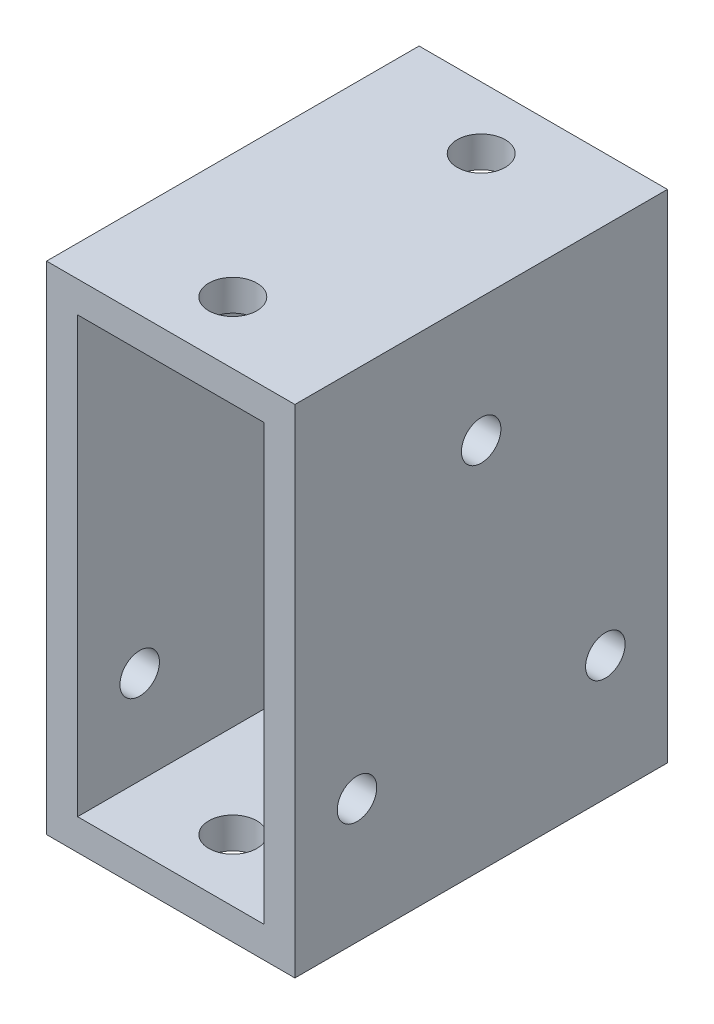
SolidWorks part; units mm, degrees
ref_plane "Front Plane" through (0, 0, 0) normal (0, 0, 1) x (1, 0, 0)
ref_plane "Top Plane" through (0, 0, 0) normal (0, 1, 0) x (1, 0, 0)
ref_plane "Right Plane" through (0, 0, 0) normal (1, 0, 0) x (0, 0, -1)
sketch "Sketch1" plane through (0, 0, 0) normal (0, 0, 1) x (1, 0, 0)
  line L0 (-9.525, 22.225) -> (9.525, 22.225)
  line L1 (-12.7, 25.4) -> (12.7, 25.4)
  line L2 (-12.7, 25.4) -> (-12.7, -25.4)
  line L3 (-12.7, -25.4) -> (12.7, -25.4)
  line L4 (12.7, 25.4) -> (12.7, -25.4)
  line L5 (-12.7, 25.4) -> (12.7, -25.4) construction
  line L6 (-12.7, -25.4) -> (12.7, 25.4) construction
  line L7 (9.525, 22.225) -> (9.525, -22.225)
  line L8 (-9.525, -22.225) -> (9.525, -22.225)
  line L9 (-9.525, 22.225) -> (-9.525, -22.225)
  point P0 (0, 0)
  dimension "D1" = 25.4
  dimension "D2" = 50.8
  dimension "D3" = 3.175
extrude "Boss-Extrude1" add sketch "Sketch1" along normal mid plane 38.1
hole_wizard "#10 (0.1935) Diameter Hole1" positions "Sketch3" profile "Sketch2" hole size "#10" standard "ANSI Inch" end condition through all
sketch "Sketch3" plane through (0, 25.4, 0) normal (0, 1, 0) x (1, 0, 0)
  line L0 (12.7, -19.05) -> (-12.7, -19.05) construction
  line L1 (0, 12.7) -> (0, -12.7) construction
  line L3 (12.7, -19.05) -> (12.7, 19.05) construction
  point P0 (0, -12.7)
  point P2 (0, 12.7)
  dimension "D1" = 25.4
  dimension "D2" = 6.35
  dimension "D3" = 12.7
sketch "Sketch2" plane through (0, 25.4, 12.7) normal (1, 0, 0) x (0, 0, 1)
  line L0 (0, 0) -> (0, 50.8)
  line L1 (0, 50.8) -> (2.4574, 50.8)
  line L2 (2.4574, 50.8) -> (2.4574, 0)
  line L5 (2.4574, 0) -> (0, 0)
  line L11 (0, -6.35) -> (0, 107.95) construction
  dimension "Thru Hole Dia." = 4.9149
  dimension "Thru Hole Depth" = 50.8
hole_wizard "#10-32 Tapped Hole1" positions "Sketch5" profile "Sketch4" tap size "#10-32" standard "ANSI Inch" end condition through all
sketch "Sketch5" plane through (-12.7, 0, 0) normal (-1, 0, 0) x (0, 0, 1)
  line L0 (-19.05, 25.4) -> (-19.05, -25.4) construction
  line L1 (-12.7, -12.7) -> (12.7, -12.7) construction
  line L3 (19.05, 25.4) -> (-19.05, 25.4) construction
  line L4 (19.05, -25.4) -> (-19.05, -25.4) construction
  point P0 (-12.7, -12.7)
  point P2 (12.7, -12.7)
  point P4 (0, 12.7)
  dimension "D1" = 19.05
  dimension "D2" = 6.35
  dimension "D3" = 25.4
  dimension "D4" = 12.7
  dimension "D5" = 12.7
sketch "Sketch4" plane through (-12.7, -12.7, -12.7) normal (0, 1, 0) x (0, 0, 1)
  line L0 (0, 0) -> (0, 25.4)
  line L1 (0, 25.4) -> (2.0193, 25.4)
  line L2 (2.0193, 25.4) -> (2.0193, 0)
  line L5 (2.0193, 0) -> (0, 0)
  line L11 (0, -6.35) -> (0, 107.95) construction
  dimension "Thread Major Dia." = 4.0386
  dimension "Thru Tap Drill Depth" = 25.4
